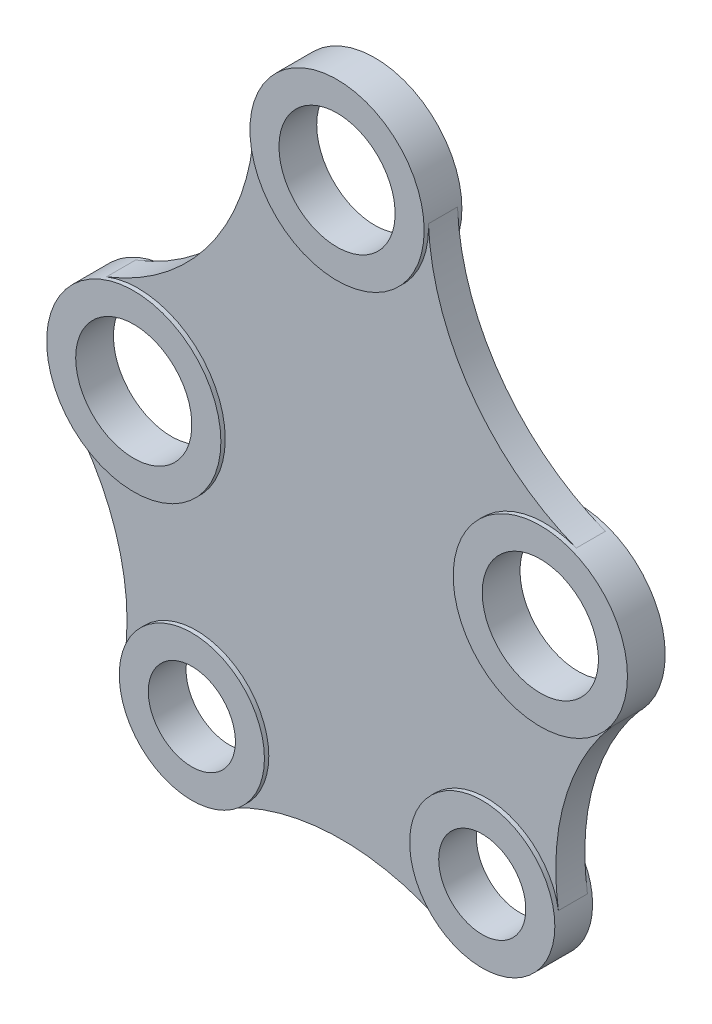
SolidWorks part; units mm, degrees
ref_plane "Front Plane" through (0, 0, 0) normal (0, 0, 1) x (1, 0, 0)
ref_plane "Top Plane" through (0, 0, 0) normal (0, 1, 0) x (1, 0, 0)
ref_plane "Right Plane" through (0, 0, 0) normal (1, 0, 0) x (0, 0, -1)
sketch "Sketch1" plane through (0, 0, 0) normal (0, 0, 1) x (1, 0, 0)
  line L0 (0, 0) -> (0, 55566.6552) construction
  line L1 (0, 0) -> (55566.6552, 0) construction
  circle A0 centre (0, 0) radius 20
  circle A1 centre (0, 0) radius 30
  circle A2 centre (-70, -98) radius 20
  circle A3 centre (-70, -98) radius 30
  circle A4 centre (-50, -185) radius 15
  circle A5 centre (-50, -185) radius 25
  arc A6 (-29.9748, 1.2288) -> (-80.8839, -70.044) centre (-109.9077, 4.5055) cw
  arc A7 (-92.8576, -117.4302) -> (-74.7169, -181.2486) centre (-153.8111, -169.2439) cw
  arc A8 (92.8576, -117.4302) -> (74.7169, -181.2486) centre (153.8111, -169.2439) ccw
  arc A9 (29.9748, 1.2288) -> (80.8839, -70.044) centre (109.9077, 4.5055) ccw
  circle A10 centre (50, -185) radius 25
  circle A11 centre (50, -185) radius 15
  circle A12 centre (70, -98) radius 30
  circle A13 centre (70, -98) radius 20
  arc A14 (-38.0952, -206.9836) -> (38.0952, -206.9836) centre (0, -277.3309) cw
  dimension "D1" = 40
  dimension "D2" = 60
  dimension "D3" = 40
  dimension "D4" = 60
  dimension "D9" = 30
  dimension "D10" = 50
  dimension "D11" = 80
  dimension "D12" = 80
  dimension "D13" = 80
  dimension "D5" = 70
  dimension "D6" = 98
  dimension "D7" = 87
  dimension "D8" = 100
extrude "Boss-Extrude1" add sketch "Sketch1" along normal mid plane 13 contours A1 A0 | A3 A2 | A5 A4 | A12 A13 | A10 A11 region at (-0.5971, -29.1454, 0) region at (94.0636, -81.5455, 0) region at (-53.5455, -73.9364, 0) region at (74.224, -183.1721, 0) region at (-48.1721, -160.776, 0)
extrude "Boss-Extrude2" add sketch "Sketch1<3>" along normal mid plane 10 contours A5 A14 A10 A8 A12 A9 A1 A6 A3 A7 region at (0, -109.3856, 0)
sketch "Sketch1<3>" plane through (0, 0, 0) normal (0, 0, 1) x (1, 0, 0) same geometry as "Sketch1"
